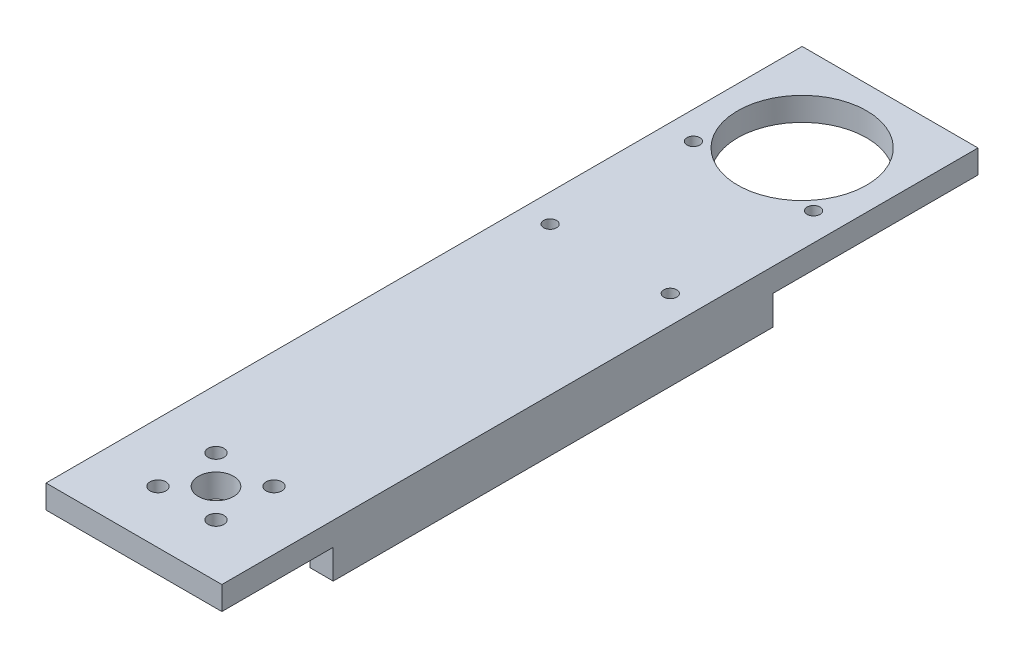
SolidWorks part; units mm, degrees
ref_plane "Front Plane" through (0, 0, 0) normal (0, 0, 1) x (1, 0, 0)
ref_plane "Top Plane" through (0, 0, 0) normal (0, 1, 0) x (1, 0, 0)
ref_plane "Right Plane" through (0, 0, 0) normal (1, 0, 0) x (0, 0, -1)
ref_plane "PZ_m115_000" through (0, 0, -115) normal (0, 0, 1) x (1, 0, 0)
sketch "S_box1" plane through (0, 0, -115) normal (0, 0, 1) x (1, 0, 0)
  line L0 (-15, -22.625) -> (15, -22.625)
  line L1 (15, -22.625) -> (15, -18.625)
  line L2 (15, -18.625) -> (-15, -18.625)
  line L3 (-15, -18.625) -> (-15, -22.625)
  dimension "P1" = 15
  dimension "P2" = 22.625
  dimension "P3" = 15
  dimension "P4" = 22.625
  dimension "P5" = 15
  dimension "P6" = 18.625
  dimension "P7" = 15
  dimension "P8" = 18.625
extrude "Boss_1" add sketch "S_box1" along normal blind 129
ref_plane "PZ_m80_000" through (0, 0, -80) normal (0, 0, 1) x (1, 0, 0)
sketch "S_box2" plane through (0, 0, -80) normal (0, 0, 1) x (1, 0, 0)
  line L0 (-15, -27.625) -> (-11, -27.625)
  line L1 (-11, -27.625) -> (-11, -22.125)
  line L2 (-11, -22.125) -> (-15, -22.125)
  line L3 (-15, -22.125) -> (-15, -27.625)
  dimension "P1" = 15
  dimension "P2" = 27.625
  dimension "P3" = 11
  dimension "P4" = 27.625
  dimension "P5" = 11
  dimension "P6" = 22.125
  dimension "P7" = 15
  dimension "P8" = 22.125
extrude "Boss_2" add sketch "S_box2" along normal blind 75
sketch "S_box3" plane through (0, 0, -80) normal (0, 0, 1) x (1, 0, 0)
  line L0 (11, -27.625) -> (15, -27.625)
  line L1 (15, -27.625) -> (15, -22.125)
  line L2 (15, -22.125) -> (11, -22.125)
  line L3 (11, -22.125) -> (11, -27.625)
  dimension "P1" = 11
  dimension "P2" = 27.625
  dimension "P3" = 15
  dimension "P4" = 27.625
  dimension "P5" = 15
  dimension "P6" = 22.125
  dimension "P7" = 11
  dimension "P8" = 22.125
extrude "Boss_3" add sketch "S_box3" along normal blind 75
ref_plane "PY_m22_725" through (0, -22.725, 0) normal (0, 1, 0) x (1, 0, 0)
sketch "S_hole4" plane through (0, -22.725, 0) normal (0, 1, 0) x (1, 0, 0)
  circle A0 centre (0, 0) radius 3
  dimension "D1_S_hole4" = 6
extrude "Hole_4" cut sketch "S_hole4" along normal blind 4.2
sketch "S_hole5" plane through (0, -22.725, 0) normal (0, 1, 0) x (1, 0, 0)
  circle A0 centre (4.9497, -4.9497) radius 1.35
  dimension "D1_S_hole5" = 2.7
  dimension "P2" = 4.9497
  dimension "P3" = 4.9497
extrude "Hole_5" cut sketch "S_hole5" along normal blind 4.2
sketch "S_hole6" plane through (0, -22.725, 0) normal (0, 1, 0) x (1, 0, 0)
  circle A0 centre (-4.9497, -4.9497) radius 1.35
  dimension "D1_S_hole6" = 2.7
  dimension "P2" = 4.9497
  dimension "P3" = 4.9497
extrude "Hole_6" cut sketch "S_hole6" along normal blind 4.2
sketch "S_hole7" plane through (0, -22.725, 0) normal (0, 1, 0) x (1, 0, 0)
  circle A0 centre (-4.9497, 4.9497) radius 1.35
  dimension "D1_S_hole7" = 2.7
  dimension "P2" = 4.9497
  dimension "P3" = 4.9497
extrude "Hole_7" cut sketch "S_hole7" along normal blind 4.2
sketch "S_hole8" plane through (0, -22.725, 0) normal (0, 1, 0) x (1, 0, 0)
  circle A0 centre (4.9497, 4.9497) radius 1.35
  dimension "D1_S_hole8" = 2.7
  dimension "P2" = 4.9497
  dimension "P3" = 4.9497
extrude "Hole_8" cut sketch "S_hole8" along normal blind 4.2
sketch "S_hole9" plane through (0, -22.725, 0) normal (0, 1, 0) x (1, 0, 0)
  circle A0 centre (0, 100) radius 11
  dimension "D1_S_hole9" = 22
  dimension "P2" = 100
extrude "Hole_9" cut sketch "S_hole9" along normal blind 4.2
sketch "S_hole10" plane through (0, -22.725, 0) normal (0, 1, 0) x (1, 0, 0)
  circle A0 centre (-10.25, 91.7) radius 1.1
  dimension "D1_S_hole10" = 2.2
  dimension "P2" = 10.25
  dimension "P3" = 91.7
extrude "Hole_10" cut sketch "S_hole10" along normal blind 4.2
sketch "S_hole11" plane through (0, -22.725, 0) normal (0, 1, 0) x (1, 0, 0)
  circle A0 centre (10.25, 91.7) radius 1.1
  dimension "D1_S_hole11" = 2.2
  dimension "P2" = 10.25
  dimension "P3" = 91.7
extrude "Hole_11" cut sketch "S_hole11" along normal blind 4.2
sketch "S_hole12" plane through (0, -22.725, 0) normal (0, 1, 0) x (1, 0, 0)
  circle A0 centre (-10.25, 67.25) radius 1.1
  dimension "D1_S_hole12" = 2.2
  dimension "P2" = 10.25
  dimension "P3" = 67.25
extrude "Hole_12" cut sketch "S_hole12" along normal blind 4.2
sketch "S_hole13" plane through (0, -22.725, 0) normal (0, 1, 0) x (1, 0, 0)
  circle A0 centre (10.25, 67.25) radius 1.1
  dimension "D1_S_hole13" = 2.2
  dimension "P2" = 10.25
  dimension "P3" = 67.25
extrude "Hole_13" cut sketch "S_hole13" along normal blind 4.2
equation "\"plate_t\" = 3"
equation "\"clearance\" = 0.4"
